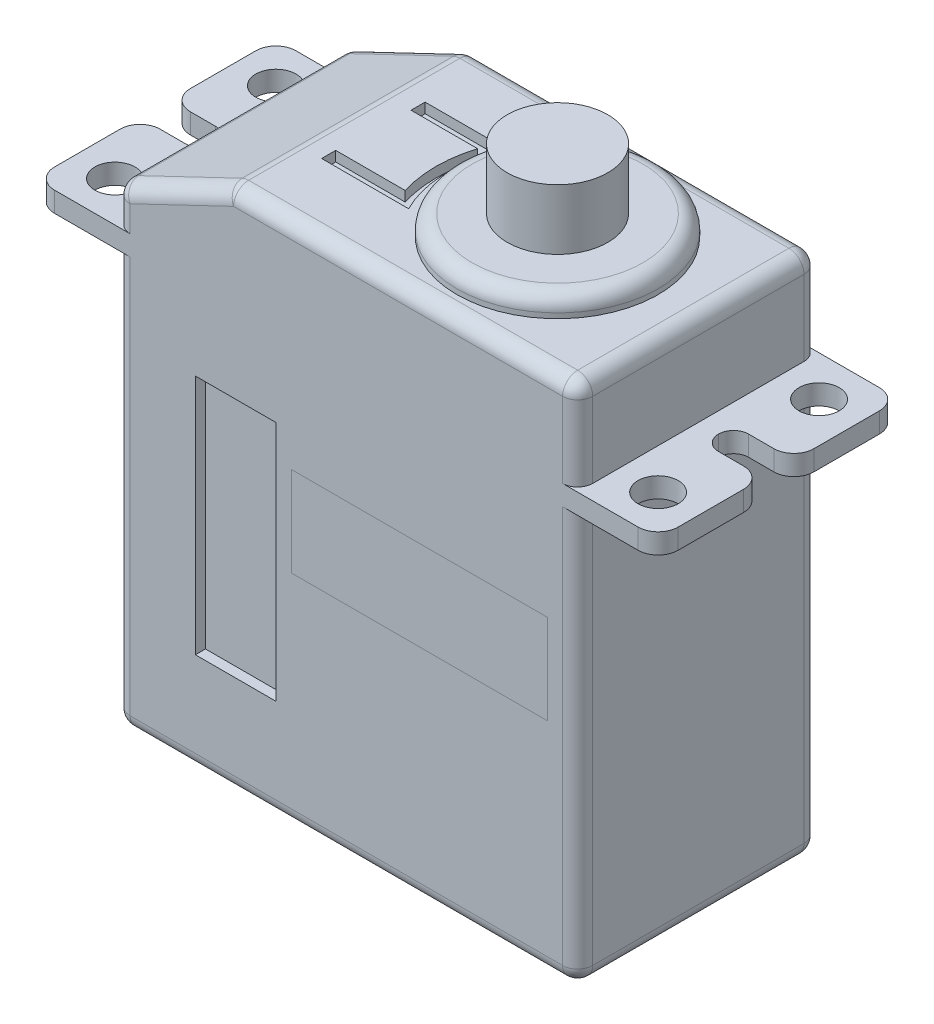
SolidWorks part; units mm, degrees
ref_plane "Front Plane" through (0, 0, 0) normal (0, 0, 1) x (1, 0, 0)
ref_plane "Top Plane" through (0, 0, 0) normal (0, 1, 0) x (1, 0, 0)
ref_plane "Right Plane" through (0, 0, 0) normal (1, 0, 0) x (0, 0, -1)
sketch "Sketch1" plane through (0, 0, 0) normal (0, 0, 1) x (1, 0, 0)
  line L1 (0, 0) -> (23, 0)
  line L2 (0, 0) -> (0, 26)
  line L3 (0, 26) -> (23, 26)
  line L4 (23, 0) -> (23, 26)
  dimension "D1" = 26
  dimension "D2" = 23
extrude "Boss-Extrude1" add sketch "Sketch1" along normal blind 12
sketch "Sketch2" plane through (0, 0, 12) normal (0, 0, 1) x (1, 0, 0)
  line L0 (5.726, 26) -> (0, 23.2609)
  line L1 (23, 26) -> (0, 26) construction
  line L2 (0, 26) -> (0, 0) construction
  line L3 (0, 23.2609) -> (0, 26)
  line L4 (0, 26) -> (5.726, 26)
extrude "Cut-Extrude1" cut sketch "Sketch2" against normal blind 12
sketch "Sketch3" plane through (0, 0, 0) normal (-1, 0, 0) x (0, 0, 1)
  line L0 (0, 23.2609) -> (0, 0) construction
  line L1 (0, 21.5) -> (12, 21.5)
  line L2 (0, 21.5) -> (0, 20.5)
  line L3 (0, 20.5) -> (12, 20.5)
  line L4 (12, 21.5) -> (12, 20.5)
  line L5 (12, 23.2609) -> (12, 0) construction
  line L6 (12, 0) -> (0, 0) construction
  dimension "D1" = 1
  dimension "D2" = 20.5
extrude "Boss-Extrude2" add sketch "Sketch3" along normal blind 4 and the other way blind 27
sketch "Sketch5" plane through (0, 21.5, 0) normal (0, 1, 0) x (1, 0, 0)
  line L0 (0, 0) -> (-4, 0) construction
  line L1 (27, 0) -> (23, 0) construction
  line L2 (0, -12) -> (-4, -12) construction
  line L3 (27, -12) -> (23, -12) construction
  circle A0 centre (-2, -10) radius 1
  circle A1 centre (-2, -2) radius 1
  circle A2 centre (25, -2) radius 1
  circle A3 centre (25, -10) radius 1
  point P10 (-2, 0)
  point P13 (25, 0)
  dimension "D5" = 2
  dimension "D1" = 2
  dimension "D2" = 2
  dimension "D3" = 2
  dimension "D4" = 2
extrude "Cut-Extrude2" cut sketch "Sketch5" against normal blind 5
sketch "Sketch6" plane through (0, 21.5, 0) normal (0, 1, 0) x (1, 0, 0)
  line L0 (-4, -12) -> (-4, 0) construction
  line L1 (-4, -5.25) -> (-1, -5.25)
  line L2 (-4, -5.25) -> (-4, -6.75)
  line L3 (-4, -6.75) -> (-1, -6.75)
  line L4 (-1, -5.25) -> (-1, -6.75)
  line L5 (27, -12) -> (27, 0) construction
  line L6 (27, -5.25) -> (24, -5.25)
  line L7 (27, -5.25) -> (27, -6.75)
  line L8 (27, -6.75) -> (24, -6.75)
  line L9 (24, -5.25) -> (24, -6.75)
  point P12 (-4, -6)
  point P13 (-1, -6)
  point P14 (27, -6)
  point P15 (24, -6)
  dimension "D1" = 1.5
  dimension "D2" = 1.5
  dimension "D3" = 3
  dimension "D4" = 3
extrude "Cut-Extrude3" cut sketch "Sketch6" against normal blind 5
fillet "Fillet1" radius 1 8 edges at (-4, 21, 5.25) (27, 21, 0) (27, 21, 5.25) (27, 21, 6.75) (27, 21, 12) (-4, 21, 12) (-4, 21, 6.75) (-4, 21, 0)
fillet "Fillet2" radius 0.75 4 edges at (-1, 21, 6.75) (-1, 21, 5.25) (24, 21, 6.75) (24, 21, 5.25)
sketch "Sketch7" plane through (0, 26, 0) normal (0, 1, 0) x (1, 0, 0)
  line L0 (23, -12) -> (23, 0) construction
  line L1 (23, -12) -> (23, 0) construction
  circle A0 centre (16, -6) radius 5
  point P4 (23, -6)
  dimension "D1" = 10
  dimension "D2" = 7
extrude "Boss-Extrude3" add sketch "Sketch7" along normal blind 1
sketch "Sketch8" plane through (0, 26, 0) normal (0, 1, 0) x (1, 0, 0)
  line L0 (11.1019, -3.5) -> (6.9174, -3.5)
  line L1 (6.9174, -3.5) -> (6.9174, -4.2)
  line L2 (6.9174, -4.2) -> (10.2291, -4.2)
  line L3 (6.7735, -8.5) -> (11.1019, -8.5)
  line L4 (6.7735, -8.5) -> (6.7735, -7.8)
  line L5 (6.7735, -7.8) -> (10.2291, -7.8)
  line L6 (23, 0) -> (5.726, 0) construction
  line L7 (23, -12) -> (5.726, -12) construction
  arc A0 (11.1019, -3.5) -> (11.1019, -8.5) centre (16, -6) ccw
  arc A1 (10.2291, -4.2) -> (10.2291, -7.8) centre (16, -6) ccw
  dimension "D1" = 0.7
  dimension "D2" = 0.7
  dimension "D3" = 3.5
  dimension "D4" = 3.5
extrude "Cut-Extrude4" cut sketch "Sketch8" against normal blind 0.5
fillet "Fillet3" radius 0.75 20 edges at (23, 0, 6) (11.5, 0, 12) (0, 0, 6) (0, 22.3805, 0) (0, 22.3805, 12) (0, 10.25, 12) (0, 10.25, 0) (11.5, 0, 0) (23, 26, 6) (23, 23.75, 12) (23, 10.25, 12) (23, 10.25, 0) (23, 23.75, 0) (16, 27, 11) (14.363, 26, 12) (2.863, 24.6305, 12) (0, 23.2609, 6) (2.863, 24.6305, 0) (5.726, 26, 6) (14.363, 26, 0)
sketch "Sketch9" plane through (0, 0, 12) normal (0, 0, 1) x (1, 0, 0)
  line L0 (22.25, 0) -> (0.75, 0) construction
  line L1 (4, 17) -> (8, 17)
  line L2 (4, 17) -> (4, 5)
  line L3 (4, 5) -> (8, 5)
  line L4 (8, 17) -> (8, 5)
  line L5 (0, 0.75) -> (0, 20.5) construction
  dimension "D1" = 12
  dimension "D2" = 4
  dimension "D3" = 5
  dimension "D4" = 4
extrude "Cut-Extrude5" cut sketch "Sketch9" against normal blind 0.5
sketch "Sketch10" plane through (0, 27, 0) normal (0, 1, 0) x (1, 0, 0)
  circle A0 centre (16, -6) radius 2.5
  dimension "D1" = 5
extrude "Boss-Extrude4" add sketch "Sketch10" along normal blind 3
sketch "Sketch11" plane through (0, 0, 12) normal (0, 0, 1) x (1, 0, 0)
  line L1 (8.7709, 15.3612) -> (21.4934, 15.3612)
  line L2 (8.7709, 15.3612) -> (8.7709, 10.9063)
  line L3 (8.7709, 10.9063) -> (21.4934, 10.9063)
  line L4 (21.4934, 15.3612) -> (21.4934, 10.9063)
split line "Split Line1"
sketch "Sketch12" plane through (0, 0, 0) normal (0, -1, 0) x (1, 0, 0)
sketch "Sketch13" plane through (0, 26, 0) normal (0, 1, 0) x (1, 0, 0)
sketch "Sketch14" plane through (0, 26, 0) normal (0, 1, 0) x (1, 0, 0)
sketch "Sketch15" plane through (0, 0, 0) normal (0, -1, 0) x (1, 0, 0)
  line L0 (-4, 7.75) -> (-4, 11) construction
  line L1 (27, 7.75) -> (27, 11) construction
  line L2 (22.25, 0) -> (0.75, 0) construction
  line L3 (0.75, 12) -> (22.25, 12) construction
  circle A0 centre (-2, 10) radius 1 construction
  circle A1 centre (25, 10) radius 1 construction
  dimension "D2" = 27
  dimension "D1" = 31
  dimension "D3" = 12
sketch "Sketch16" plane through (0, 26, 0) normal (0, 1, 0) x (1, 0, 0)
sketch "Sketch18" plane through (0, 0, 0) normal (0, 0, -1) x (-1, 0, 0)
  line L0 (-22.25, 26) -> (-5.8962, 26) construction
  line L1 (-26, 21.5) -> (-22.25, 21.5) construction
sketch "Sketch19" plane through (0, 0, 0) normal (0, 0, -1) x (-1, 0, 0)
  line L0 (-23, 21.5) -> (-23, 25.25) construction
  line L1 (-27, 20.5) -> (-27, 21.5) construction
sketch "Sketch20" plane through (0, 26, 0) normal (0, 1, 0) x (1, 0, 0)
  line L0 (27, -4.25) -> (27, -1) construction
  circle A0 centre (16, -6) radius 2.5 construction
sketch "Sketch21" plane through (0, 27, 0) normal (0, 1, 0) x (1, 0, 0)
  line L0 (-4, -4.25) -> (-4, -1) construction
  circle A0 centre (16, -6) radius 2.5 construction
sketch "Sketch22" plane through (0, 26, 0) normal (0, 1, 0) x (1, 0, 0)
  line L0 (5.8962, 0) -> (22.25, 0) construction
  circle A0 centre (16, -6) radius 2.5 construction
sketch "Sketch23" plane through (0, 0, 0) normal (0, 0, -1) x (-1, 0, 0)
  line L0 (-26, 21.5) -> (-22.25, 21.5) construction
  line L1 (-22.25, 26) -> (-5.8962, 26) construction
  dimension "D1" = 4.5
sketch "Sketch24" plane through (-9.0549, 18.9295, 0) normal (-0.4315, 0.9021, 0) x (0.9021, 0.4315, 0)
  line L0 (9.2777, -0.75) -> (9.2777, -11.25) construction
  line L1 (31.7177, -11.25) -> (31.7177, -0.75) construction
sketch "Sketch25" plane through (0, 26, 0) normal (0, 1, 0) x (1, 0, 0)
  line L0 (23, -11.25) -> (23, -0.75) construction
  line L2 (0, -0.75) -> (0, -11.25) construction
  circle A0 centre (16, -6) radius 2.5 construction
  point P6 (0, -2.0163)
  dimension "D1" = 7
  dimension "D2" = 16
